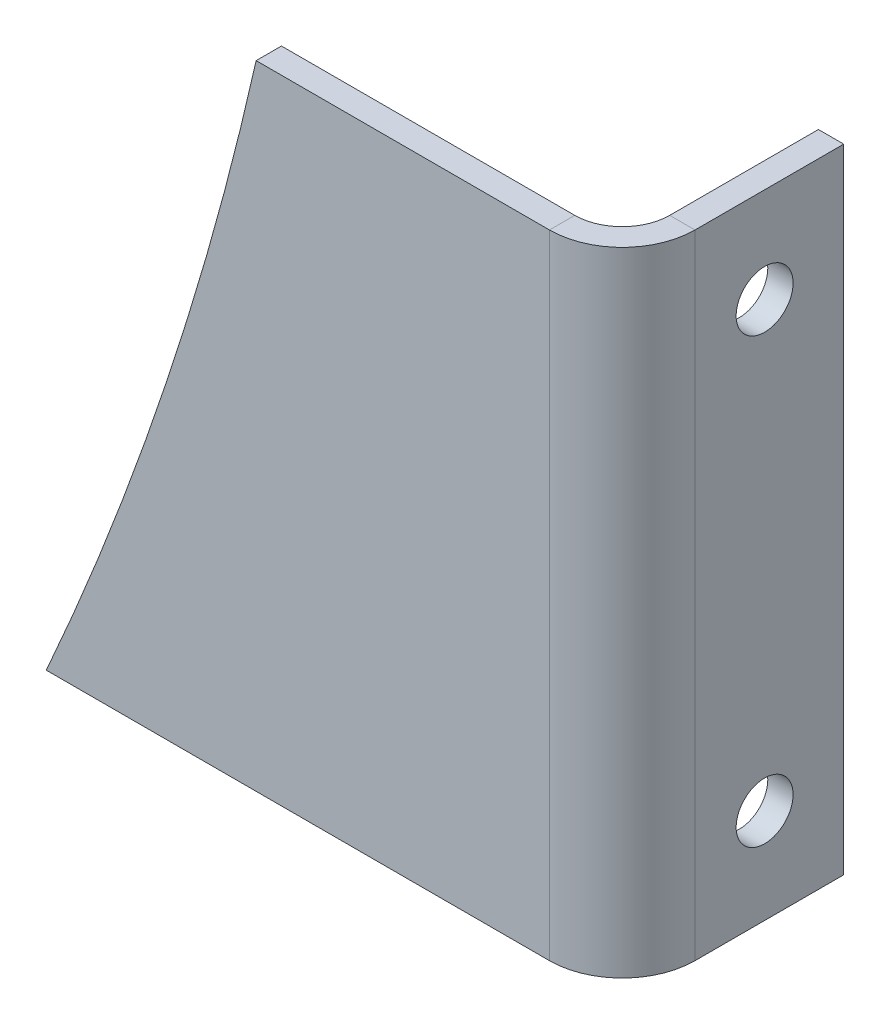
SolidWorks part; units mm, degrees
note: The reader was unsure of these and kept them because the rebuilt part matched: thickness of "Base-Flange1", "Edge-Flange1", "Sheet-Metal3", "Sheet-Metal4", "Sheet-Metal5", "Sheet-Metal6"; flange length of "Edge-Flange1".
material "A516-Gr70"
ref_plane "Front Plane" through (0, 0, 0) normal (0, 0, 1) x (1, 0, 0)
ref_plane "Top Plane" through (0, 0, 0) normal (0, 1, 0) x (1, 0, 0)
ref_plane "Right Plane" through (0, 0, 0) normal (1, 0, 0) x (0, 0, -1)
sketch "Sketch1" plane through (0, 0, 0) normal (1, 0, 0) x (0, 0, -1)
  line L1 (35, -100) -> (-35, -100)
  line L2 (35, -100) -> (35, 100)
  line L3 (35, 100) -> (-35, 100)
  line L4 (-35, -100) -> (-35, 100)
  line L5 (35, -100) -> (-35, 100) construction
  line L6 (35, 100) -> (-35, -100) construction
  point P0 (0, 0)
  dimension "D1" = 70
  dimension "D2" = 200
base flange "Base-Flange1" sketch "Sketch1" thickness 8 reverse thickness direction no parameters "D1"=0
edge flange "Edge-Flange1" sketch "Sketch8" flange angle 90 flange length 250 flange position material inside bend radius 15 thickness 8 relief rectangular parameters "D6"=10
sketch "Sketch8" plane through (-8, 0, 35) normal (0, 0, -1) x (0, -1, 0)
  line L1 (100, 0) -> (-100, 0) construction
  line L2 (-100, 0) -> (-100, 242)
  line L3 (-100, 242) -> (100, 242)
  line L4 (100, 242) -> (100, 0)
  line L5 (100, 0) -> (-100, 0)
bend "EdgeBend1" bend radius 15 bend angle 90 parameters "D5"=1
sketch "Sketch9" plane through (0, 0, 35) normal (0, 0, 1) x (1, 0, 0)
  line L0 (0, 100) -> (0, -100) construction
  circle A0 centre (-1150, 332) radius 1060
  dimension "D1" = 2120
  dimension "D2" = 332
  dimension "D3" = 1150
extrude "Cut-Extrude1" cut sketch "Sketch9" against normal blind 10 normal cut yes
sketch "Sketch10" plane through (0, 0, 0) normal (1, 0, 0) x (0, 0, -1)
  line L0 (35, -100) -> (35, 100) construction
  circle A0 centre (10, -70) radius 9
  circle A1 centre (10, 70) radius 9
  dimension "D1" = 18
  dimension "D2" = 18
  dimension "D3" = 70
  dimension "D4" = 70
  dimension "D5" = 25
extrude "Cut-Extrude2" cut sketch "Sketch10" against normal blind 10 normal cut yes
sketch "Bend-Lines1" [suppressed] plane through (0, 0, 0) normal (0, 1, 0) x (1, 0, 0)
sketch "Bounding-Box1" [suppressed] plane through (0, 0, 0) normal (0, 1, 0) x (1, 0, 0)
sheet metal parameters "Sheet-Metal3" thickness 8 parameters "D1"=0
flat pattern "Flat-Pattern3" [suppressed]
sketch "Bend-Lines2" plane through (0, 0, 0) normal (0, 1, 0) x (1, 0, 0)
sketch3d "Bounding-Box2" [suppressed]
  line L0 (-30, 400, 0) -> (-30, -400, 0) construction
  line L1 (30, 400, 0) -> (30, -400, 0) construction
  line L2 (-30, 400, 0) -> (30, 400, 0) construction
  line L3 (-30, -400, 0) -> (30, -400, 0) construction
sheet metal parameters "Sheet-Metal4" thickness 8 parameters "D1"=0, "D7"=6
flat pattern "Flat-Pattern3"
sketch "Bend-Lines2" plane through (0, 0, 0) normal (1, 0, 0) x (0, 0, -1)
  line L0 (-26.3562, -500) -> (-26.3562, 500) construction
  line L1 (-26.3562, -500) -> (-26.3562, 500) construction
sketch3d "Bounding-Box2" [suppressed]
  line L0 (30, 500, 0) -> (30, -500, 0) construction
  line L1 (-222.7124, 500, 0) -> (-222.7124, -500, 0) construction
  line L2 (30, 500, 0) -> (-222.7124, 500, 0) construction
  line L3 (30, -500, 0) -> (-222.7124, -500, 0) construction
bend of the flat pattern "Flatten-<EdgeBend1>1"
sheet metal parameters "Sheet-Metal5" thickness 8 parameters "D1"=0, "D7"=6
flat pattern "Flat-Pattern3"
sketch "Bend-Lines2" plane through (0, 0, 0) normal (1, 0, 0) x (0, 0, -1)
  line L0 (-20.708, 100) -> (-20.708, -100) construction
  line L1 (-20.708, 100) -> (-20.708, -100) construction
sketch3d "Bounding-Box2" [suppressed]
  line L0 (30, 100, 0) -> (30, -100, 0) construction
  line L1 (-137.2536, 100, 0) -> (-137.2536, -100, 0) construction
  line L2 (30, 100, 0) -> (-137.2536, 100, 0) construction
  line L3 (30, -100, 0) -> (-137.2536, -100, 0) construction
bend of the flat pattern "Flatten-<EdgeBend1>1"
sheet metal parameters "Sheet-Metal6" thickness 8 parameters "D1"=0, "D7"=6
flat pattern "Flat-Pattern3"
sketch "Bend-Lines2" plane through (0, 0, 0) normal (1, 0, 0) x (0, 0, -1)
  line L0 (-26.9226, 100) -> (-26.9226, -100) construction
  line L1 (-26.9226, 100) -> (-26.9226, -100) construction
sketch3d "Bounding-Box2" [suppressed]
  line L0 (-200.8699, -100, 0) -> (35, -100, 0) construction
  line L1 (-200.8699, 100, 0) -> (35, 100, 0) construction
  line L2 (-200.8699, -100, 0) -> (-200.8699, 100, 0) construction
  line L3 (35, -100, 0) -> (35, 100, 0) construction
bend of the flat pattern "Flatten-<EdgeBend1>1"
